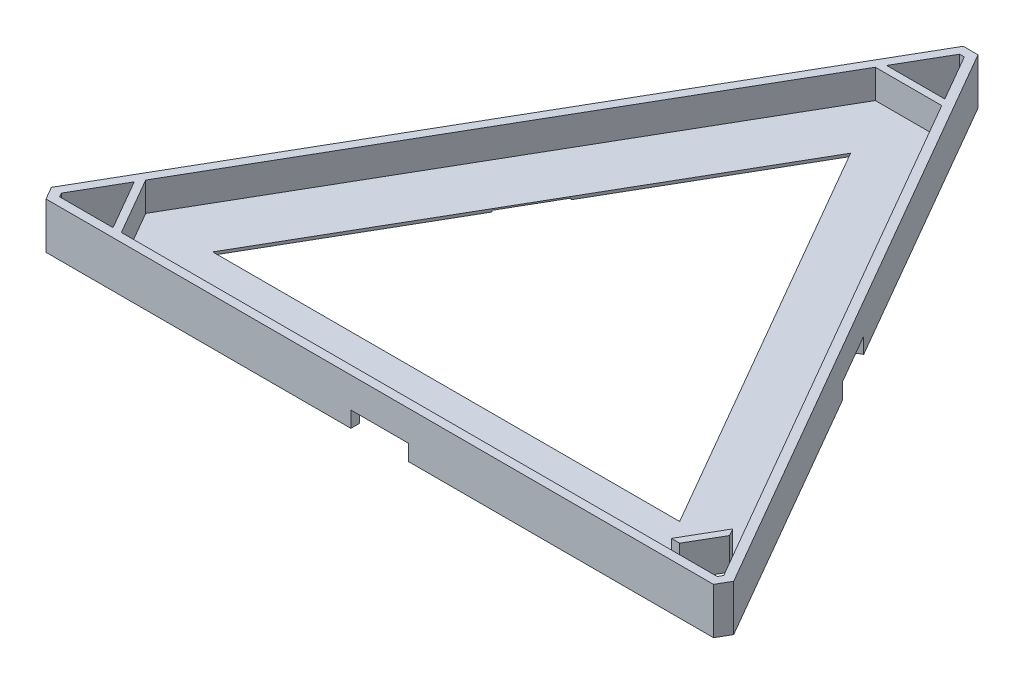
SolidWorks part; units mm, degrees
ref_plane "Front Plane" through (0, 0, 0) normal (0, 0, 1) x (1, 0, 0)
ref_plane "Top Plane" through (0, 0, 0) normal (0, 1, 0) x (1, 0, 0)
ref_plane "Right Plane" through (0, 0, 0) normal (1, 0, 0) x (0, 0, -1)
sketch "Sketch1" plane through (0, 0, 0) normal (0, 1, 0) x (1, 0, 0)
  line L0 (351.2729, 67.6655) -> (468.273, -134.9846)
  line L1 (347.2728, 67.6655) -> (347.2728, 65.1655) construction
  line L2 (409.773, -33.6595) -> (407.6079, -34.9095) construction
  line L3 (468.273, -134.9846) -> (464.2732, -141.9124)
  line L4 (230.2733, -141.9124) -> (464.2732, -141.9124)
  line L5 (230.2733, -141.9124) -> (226.2727, -134.9842)
  line L6 (226.2727, -134.9842) -> (343.2728, 67.6655)
  line L7 (353.4142, 63.9567) -> (351.2491, 62.7067) construction
  line L8 (347.2733, -141.9124) -> (347.2733, -139.4124) construction
  line L9 (231.7167, -139.4124) -> (462.8299, -139.4124)
  line L10 (284.7727, -33.6594) -> (286.9378, -34.9094) construction
  line L11 (344.7161, 65.1655) -> (349.8295, 65.1655)
  line L12 (465.3862, -134.9846) -> (349.8295, 65.1655)
  line L13 (466.2731, -138.4485) -> (464.1081, -137.1985) construction
  line L14 (462.8299, -139.4124) -> (465.3862, -134.9846)
  line L15 (229.1594, -134.9842) -> (344.7161, 65.1655)
  line L16 (229.1594, -134.9842) -> (231.7167, -139.4124)
  line L17 (286.9378, -34.9094) -> (287.3708, -35.1594) construction
  line L18 (230.438, -137.1983) -> (230.871, -136.9483) construction
  line L19 (232.0053, -138.9123) -> (229.7368, -134.9842)
  line L20 (343.2728, 67.6655) -> (351.2729, 67.6655)
  line L21 (345.0048, 64.6655) -> (229.7368, -134.9842)
  line L22 (349.5409, 64.6655) -> (345.0048, 64.6655)
  line L23 (249.0568, -126.4468) -> (246.8918, -127.697) construction
  line L24 (407.6079, -34.9095) -> (407.1749, -35.1595) construction
  line L26 (233.4463, -136.4089) -> (251.9226, -136.4093)
  line L27 (464.8089, -134.9846) -> (462.5412, -138.9123)
  line L28 (462.5412, -138.9123) -> (232.0053, -138.9123)
  line L29 (251.9226, -136.4093) -> (241.8609, -118.9847)
  line L30 (241.8609, -118.9847) -> (232.6236, -134.9842)
  line L31 (232.6236, -134.9842) -> (233.4463, -136.4089)
  line L33 (287.3708, -35.1594) -> (289.5359, -36.4094) construction
  line L34 (254.8093, -136.4089) -> (243.3042, -116.4848)
  line L35 (335.7675, 43.666) -> (243.3042, -116.4848)
  line L36 (358.7782, 43.666) -> (335.7675, 43.666)
  line L38 (289.5359, -36.4094) -> (306.8564, -46.4094) construction
  line L41 (461.939, -134.9846) -> (461.1164, -136.4093)
  line L42 (347.2688, -136.4172) -> (347.2688, -116.4172) construction
  line L43 (442.6021, -136.4093) -> (452.6999, -118.9847)
  line L44 (245.2636, -119.878) -> (249.0568, -126.4468) construction
  line L45 (452.6999, -118.9847) -> (461.939, -134.9846)
  line L48 (461.1164, -136.4093) -> (442.6021, -136.4093)
  line L49 (405.0134, -36.4027) -> (387.6936, -46.404) construction
  line L50 (306.8564, -46.4094) -> (466.2731, -138.4485) construction
  line L51 (357.3348, 46.166) -> (337.2109, 46.166)
  line L52 (337.2109, 46.166) -> (346.4484, 62.1659)
  line L53 (346.4484, 62.1659) -> (348.0966, 62.164)
  line L54 (348.0966, 62.164) -> (357.3348, 46.166)
  line L55 (228.273, -138.4483) -> (387.6936, -46.404) construction
  line L56 (347.2688, -116.4172) -> (347.2728, 43.666) construction
  line L57 (266.4391, -116.428) -> (428.1137, -116.4172)
  line L58 (347.2736, 23.6092) -> (428.1137, -116.4172)
  line L59 (266.4391, -116.428) -> (347.2736, 23.6092)
  line L60 (439.7283, -136.4254) -> (439.7283, -132.9254) construction
  line L61 (451.2487, -116.4715) -> (448.6507, -117.9717) construction
  line L62 (452.6999, -118.9847) -> (358.7782, 43.666)
  line L63 (442.6021, -136.4093) -> (254.8093, -136.4089)
  line L64 (441.749, -132.9254) -> (444.621, -132.9254)
  line L65 (448.6507, -117.9717) -> (450.9647, -121.979) construction
  line L66 (449.5167, -119.4714) -> (450.9647, -121.979)
  line L67 (441.749, -132.9254) -> (449.5167, -119.4714)
  line L68 (450.9647, -121.979) -> (444.621, -132.9254)
  point P13 (407.6079, -34.9095)
  point P20 (464.1081, -137.1985)
  point P23 (347.2733, -139.4124)
  point P25 (347.2732, -141.9124)
  point P27 (347.2728, 65.1655)
  point P31 (286.9378, -34.9094)
  point P37 (287.3708, -35.1594)
  point P39 (230.871, -136.9483)
  point P41 (347.2728, 64.6655)
  point P45 (407.1749, -35.1595)
  point P50 (246.8918, -127.697)
  point P56 (289.5359, -36.4094)
  point P58 (249.0568, -126.4468)
  point P60 (347.2728, 43.666)
  point P62 (345.0048, -136.4089)
  point P64 (445.4885, -126.4485)
  point P71 (447.651, -127.697)
  point P77 (347.2728, 46.166)
  point P84 (347.2688, -116.4172)
  point P87 (387.6936, -46.404)
  point P89 (306.8564, -46.4094)
  point P100 (405.0134, -36.4027)
  dimension "D1" = 2.5
  dimension "D2" = 2.5
  dimension "D3" = 2.5
  dimension "D4" = 2.5
  dimension "D5" = 2.5
  dimension "D6" = 2.5
  dimension "D7" = 0.5
  dimension "D8" = 0.5
  dimension "D9" = 0.5
  dimension "D10" = 2.5
  dimension "D11" = 2.5
  dimension "D12" = 20
  dimension "D13" = 20
  dimension "D14" = 20
  dimension "D15" = 3.5
  dimension "D16" = 3
extrude "Boss-Extrude1" add sketch "Sketch1" along normal blind 1 contours L36 L35 L34 L57 L59 L58 region at (251.4484, 0, 125.0658)
extrude "Boss-Extrude2" add sketch "Sketch1<9>" along normal blind 11 contours L28 L27 L22 L21 L19 L31 L30 L29 L26 L34 L35 L36 L41 L48 L43 L45 L53 L54 L51 L52 | L68 L64 L67 L66 region at (230.7087, 0, 137.042)
sketch "Sketch1<9>" plane through (0, 0, 0) normal (0, 1, 0) x (1, 0, 0) same geometry as "Sketch1"
extrude "Boss-Extrude3" add sketch "Sketch1<10>" along normal blind 10 and the other way blind 5 contours L28 L27 L22 L21 L19 L31 L30 L29 L26 L34 L35 L36 L41 L48 L43 L45 L53 L54 L51 L52 region at (230.7087, 0, 137.042)
sketch "Sketch1<10>" plane through (0, 0, 0) normal (0, 1, 0) x (1, 0, 0) same geometry as "Sketch1"
sketch "Sketch3" plane through (290.5896, 0, -167.772) normal (0.866, 0, -0.5) x (-0.5, 0, -0.866)
  line L1 (-246.593, -10.5) -> (-226.593, -10.5)
  line L2 (-246.593, -10.5) -> (-246.593, 0.5)
  line L3 (-246.593, 0.5) -> (-226.593, 0.5)
  line L4 (-226.593, -10.5) -> (-226.593, 0.5)
  line L5 (-246.593, -10.5) -> (-226.593, 0.5) construction
  line L6 (-246.593, 0.5) -> (-226.593, -10.5) construction
  point P0 (-236.593, -5)
  dimension "D1" = 20
  dimension "D2" = 11
extrude "Cut-Extrude3" cut sketch "Sketch3" against normal blind 25
sketch "Sketch5" plane through (0, 0, 139.4124) normal (0, 0, 1) x (1, 0, 0)
  line L0 (231.7167, -5) -> (462.8299, -5) construction
  line L1 (337.2733, -10.5) -> (357.2733, -10.5)
  line L2 (337.2733, -10.5) -> (337.2733, 0.5)
  line L3 (337.2733, 0.5) -> (357.2733, 0.5)
  line L4 (357.2733, -10.5) -> (357.2733, 0.5)
  line L5 (337.2733, -10.5) -> (357.2733, 0.5) construction
  line L6 (337.2733, 0.5) -> (357.2733, -10.5) construction
  point P0 (347.2733, -5)
  dimension "D1" = 20
  dimension "D2" = 11
extrude "Cut-Extrude4" cut sketch "Sketch5" against normal blind 25
sketch "Sketch6" plane through (230.3194, 0, 132.9752) normal (-0.866, 0, -0.5) x (-0.5, 0, 0.866)
  line L0 (2.3199, -5) -> (-228.7932, -5) construction
  line L1 (-123.2367, -10.5) -> (-103.2367, -10.5)
  line L2 (-123.2367, -10.5) -> (-123.2367, 0.5)
  line L3 (-123.2367, 0.5) -> (-103.2367, 0.5)
  line L4 (-103.2367, -10.5) -> (-103.2367, 0.5)
  line L5 (-123.2367, -10.5) -> (-103.2367, 0.5) construction
  line L6 (-123.2367, 0.5) -> (-103.2367, -10.5) construction
  point P0 (-113.2367, -5)
  dimension "D1" = 20
  dimension "D2" = 11
extrude "Cut-Extrude5" cut sketch "Sketch6" against normal blind 25
